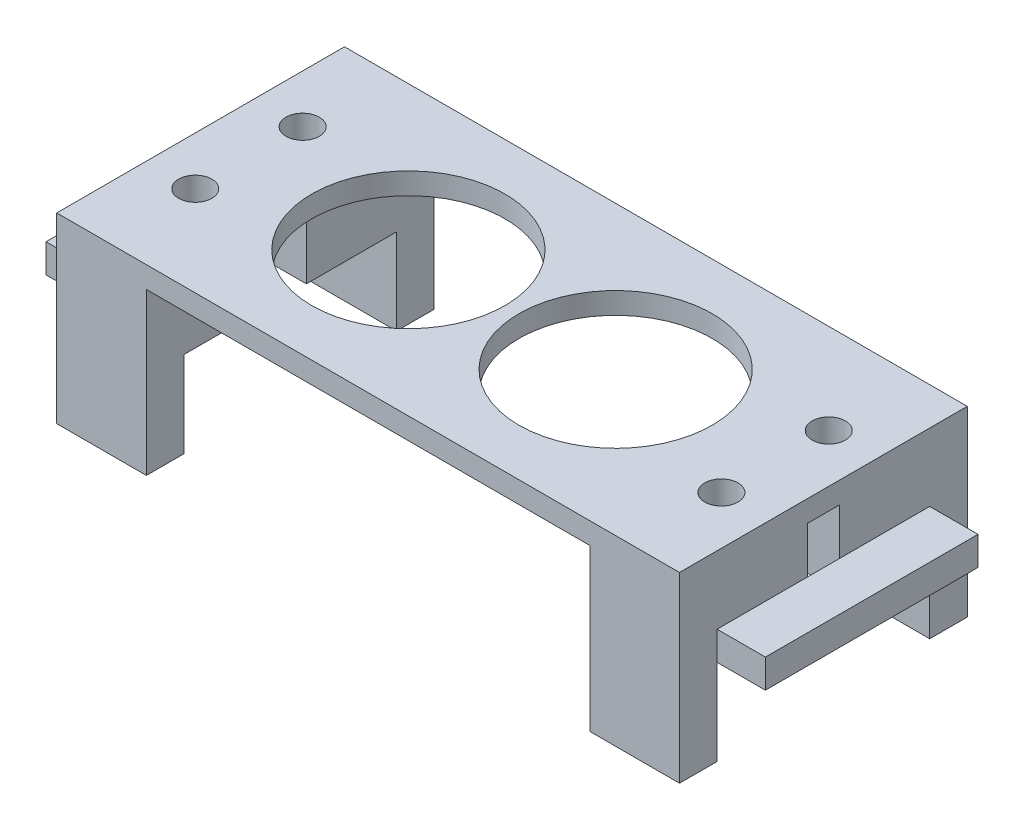
SolidWorks part; units mm, degrees
material "ABS"
ref_plane "Front Plane" through (0, 0, 0) normal (0, 0, 1) x (1, 0, 0)
ref_plane "Top Plane" through (0, 0, 0) normal (0, 1, 0) x (1, 0, 0)
ref_plane "Right Plane" through (0, 0, 0) normal (1, 0, 0) x (0, 0, -1)
sketch "Sketch2" plane through (0, 0, 0) normal (0, 1, 0) x (1, 0, 0)
  line L0 (-24.5, 5) -> (-24.5, -5) construction
  line L1 (-29, 9.9) -> (29, 9.9)
  line L2 (-29, 9.9) -> (-29, -9.9)
  line L3 (-29, -9.9) -> (29, -9.9)
  line L4 (29, 9.9) -> (29, -9.9)
  line L5 (-29, 9.9) -> (29, -9.9) construction
  line L6 (-29, -9.9) -> (29, 9.9) construction
  line L7 (-24.5, -5) -> (24.5, -5) construction
  line L8 (24.5, -5) -> (24.5, 5) construction
  line L9 (24.5, 5) -> (-24.5, 5) construction
  line L10 (-20.65, 9.9) -> (-20.65, -9.9) construction
  line L15 (20.65, 9.9) -> (20.65, -9.9) construction
  line L16 (-20.65, 0) -> (20.65, 0) construction
  circle A0 centre (-9.65, 0) radius 9
  circle A1 centre (-24.5, 5) radius 1.55
  circle A2 centre (-24.5, -5) radius 1.55
  circle A3 centre (24.5, 5) radius 1.55
  circle A4 centre (24.5, -5) radius 1.55
  circle A5 centre (9.65, 0) radius 9
  point P0 (0, 0)
  point P16 (-24.5, 0)
  point P17 (0, 5)
  point P27 (0, 0)
  dimension "D1" = 18
  dimension "D2" = 3.1
  dimension "D9" = 41.3
  dimension "D10" = 11
  dimension "D3" = 4.5
  dimension "D4" = 10
  dimension "D5" = 49
  dimension "D6" = 19.8
  dimension "D7" = 11
extrude "Boss-Extrude1" add sketch "Sketch2" along normal blind 2 contours L4 L1 L2 L3 A4 A3 A2 A1 A0 region at (0, 0, 0)
sketch "Sketch3" plane through (0, 0, 0) normal (0, -1, 0) x (1, 0, 0)
  line L0 (-20.65, 9.9) -> (-20.65, -9.9)
  line L1 (-29, 9.9) -> (29, 9.9) construction
  line L2 (-29, -9.9) -> (29, -9.9) construction
  line L3 (-20.65, -9.9) -> (-29, -9.9)
  line L4 (-29, -9.9) -> (-29, 9.9)
  line L5 (-29, 9.9) -> (-20.65, 9.9)
  line L6 (20.65, 9.9) -> (20.65, -9.9)
  line L7 (20.65, -9.9) -> (29, -9.9)
  line L8 (29, -9.9) -> (29, 9.9)
  line L9 (29, 9.9) -> (20.65, 9.9)
  line L10 (-29, 9.9) -> (29, 9.9) construction
  line L12 (-29, 1.5) -> (-20.65, 1.5)
  line L13 (-29, 1.5) -> (-29, -1.5)
  line L14 (-29, -1.5) -> (-20.65, -1.5)
  line L15 (-20.65, 1.5) -> (-20.65, -1.5)
  line L16 (20.65, 1.5) -> (29, 1.5)
  line L17 (20.65, 1.5) -> (20.65, -1.5)
  line L18 (20.65, -1.5) -> (29, -1.5)
  line L19 (29, 1.5) -> (29, -1.5)
  circle A0 centre (-24.5, -5) radius 1.55
  circle A1 centre (-24.5, 5) radius 1.55
  circle A2 centre (24.5, -5) radius 1.55
  circle A3 centre (24.5, 5) radius 1.55
  point P43 (20.65, 0)
  point P44 (-20.65, 0)
  circle M5 centre (24.5, 5) radius 1.55
  circle M6 centre (24.5, -5) radius 1.55
  circle M7 centre (-24.5, 5) radius 1.55
  circle M8 centre (-24.5, -5) radius 1.55
  line M13 (29, -9.9) -> (29, 9.9)
  line M14 (29, 9.9) -> (-29, 9.9)
  line M15 (-29, 9.9) -> (-29, -9.9)
  line M16 (-29, -9.9) -> (29, -9.9)
  dimension "D1" = 3
extrude "Boss-Extrude2" add sketch "Sketch3" along normal blind 7 contours L12 L0 M15 M14 M7 | L14 L0 M15 M16 M8 | L6 L16 L8 M14 M5 | L18 L6 M16 M13 M6 region at (-20.7684, 0, 5.7) region at (24.825, 0, 9.7816) region at (-20.7684, 0, -5.7) region at (24.825, 0, -1.6184)
sketch "Sketch6" plane through (0, 2, 0) normal (0, 1, 0) x (1, 0, 0)
  line L0 (-29, 0) -> (29, 0) construction
  line L1 (29, 9.9) -> (-29, 9.9)
  line L2 (29, 9.9) -> (29, 13.4)
  line L3 (29, 13.4) -> (-29, 13.4)
  line L4 (-29, 9.9) -> (-29, 13.4)
  line L5 (20.65, 9.9) -> (-20.65, 9.9)
  line L6 (20.65, 9.9) -> (20.65, 13.4)
  line L7 (20.65, 13.4) -> (-20.65, 13.4)
  line L8 (-20.65, 9.9) -> (-20.65, 13.4)
  line L9 (-29, 9.9) -> (-29, -9.9) construction
  line L10 (29, 9.9) -> (29, -9.9) construction
  line L12 (29, -13.4) -> (-29, -13.4)
  line L13 (-29, -9.9) -> (-29, -13.4)
  line L14 (29, -9.9) -> (-29, -9.9)
  line L15 (29, -9.9) -> (29, -13.4)
  line L16 (20.65, -13.4) -> (-20.65, -13.4)
  line L17 (-20.65, -9.9) -> (-20.65, -13.4)
  line L18 (20.65, -9.9) -> (-20.65, -9.9)
  line L19 (20.65, -9.9) -> (20.65, -13.4)
  line M12 (29, 9.9) -> (-29, 9.9)
  line M14 (-29, -9.9) -> (29, -9.9)
  dimension "D1" = 3.5
extrude "Boss-Extrude4" add sketch "Sketch6" against normal up to surface (2 mm away) contours L6 L2 L3 M12 | L8 L3 L4 M12 | L8 L1 L6 L3 | M14 | M14 | M14 | L19 L14 L17 L12 region at (24.825, 2, -11.65) region at (0, 2, -11.65) region at (-24.825, 2, -11.65) region at (24.825, 2, 11.65) region at (0, 2, 11.65) region at (-24.825, 2, 11.65) up to face at (-9.65, 0, 9)
extrude "Boss-Extrude5" add sketch "Sketch6<3>" against normal blind 17 contours L6 L2 L3 M12 | L8 L3 L4 M12 | L17 L13 L12 M14 | L19 L12 L15 M14 region at (24.825, 2, -11.65) region at (-24.825, 2, -11.65) region at (24.825, 2, 11.65) region at (-24.825, 2, 11.65)
sketch "Sketch6<3>" plane through (0, 2, 0) normal (0, 1, 0) x (1, 0, 0) same geometry as "Sketch6"
extrude "Boss-Extrude6" add sketch "Sketch6<4>" against normal up to surface (9 mm away) contours M14 | M14 | L6 L2 L3 M12 | L8 L3 L4 M12 region at (24.825, 2, -11.65) region at (-24.825, 2, -11.65) region at (24.825, 2, 11.65) region at (-24.825, 2, 11.65) up to face at (24.825, -7, -5.7)
sketch "Sketch6<4>" plane through (0, 2, 0) normal (0, 1, 0) x (1, 0, 0) same geometry as "Sketch6"
sketch "Sketch7" plane through (0, -7, 0) normal (0, -1, 0) x (1, 0, 0)
  line L1 (29, 9.9) -> (33.5, 9.9)
  line L2 (29, 9.9) -> (29, -9.9)
  line L3 (29, -9.9) -> (33.5, -9.9)
  line L4 (33.5, 9.9) -> (33.5, -9.9)
  line L5 (-29, 9.9) -> (-33.5, 9.9)
  line L6 (-29, 9.9) -> (-29, -9.9)
  line L7 (-29, -9.9) -> (-33.5, -9.9)
  line L8 (-33.5, 9.9) -> (-33.5, -9.9)
  line L9 (29, 1.5) -> (29, 9.9) construction
  line L11 (-29, -1.5) -> (-29, -9.9) construction
  line L12 (-29, -9.9) -> (-20.65, -9.9) construction
  dimension "D1" = 4.5
  dimension "D2" = 19.8
extrude "Boss-Extrude7" add sketch "Sketch7" against normal blind 2.675
